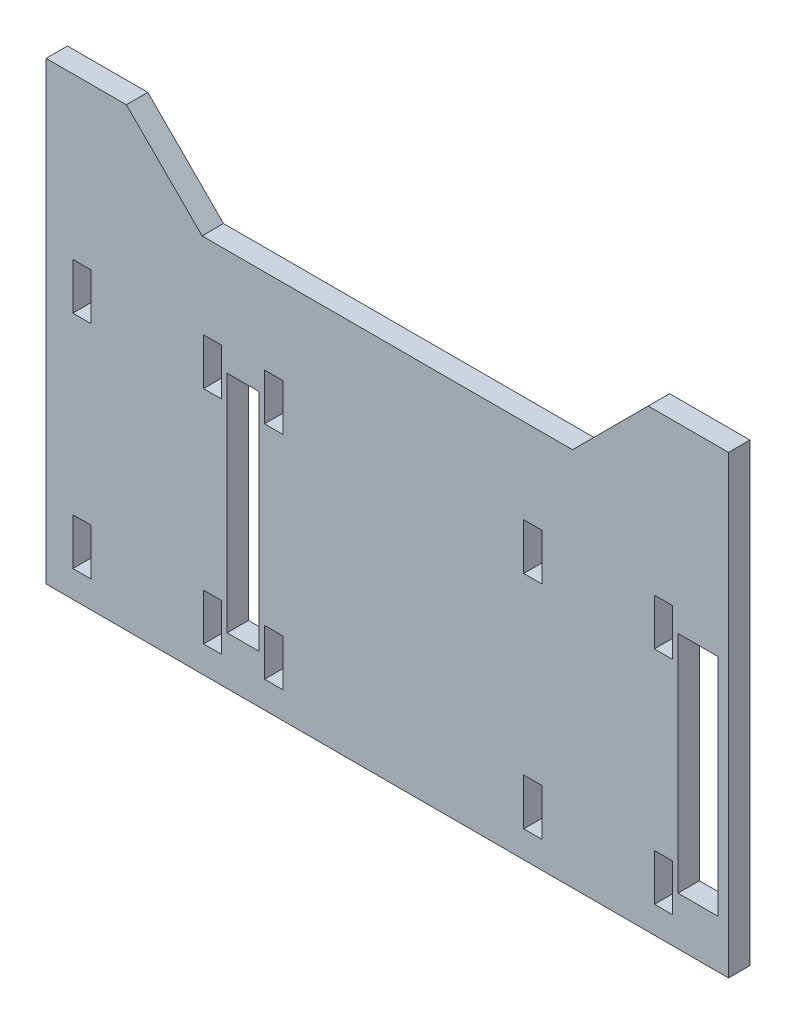
SolidWorks part; units mm, degrees
ref_plane "Front Plane" through (0, 0, 0) normal (0, 0, 1) x (1, 0, 0)
ref_plane "Top Plane" through (0, 0, 0) normal (0, 1, 0) x (1, 0, 0)
ref_plane "Right Plane" through (0, 0, 0) normal (1, 0, 0) x (0, 0, -1)
sketch "Sketch1" plane through (0, 0, 0) normal (0, 0, 1) x (1, 0, 0)
  line L0 (0, 66.0849) -> (0, -70.4198) construction
  line L6 (-37.3, 25) -> (-33.9, 25)
  line L7 (22.5, 25) -> (25.9, 25)
  line L8 (22.5, 25) -> (22.5, 16.3)
  line L9 (22.5, 16.3) -> (25.9, 16.3)
  line L10 (25.9, 25) -> (25.9, 16.3)
  line L11 (-103.5149, 0) -> (102.2922, 0) construction
  line L12 (22.5, -16.3) -> (25.9, -16.3)
  line L13 (22.5, -25) -> (22.5, -16.3)
  line L14 (25.9, -25) -> (25.9, -16.3)
  line L15 (22.5, -25) -> (25.9, -25)
  line L16 (-22.5, 25) -> (-25.9, 25)
  line L17 (-22.5, 25) -> (-22.5, 16.3)
  line L18 (-25.9, 25) -> (-25.9, 16.3)
  line L19 (-22.5, 16.3) -> (-25.9, 16.3)
  line L20 (-22.5, -16.3) -> (-25.9, -16.3)
  line L21 (-22.5, -25) -> (-22.5, -16.3)
  line L22 (-25.9, -25) -> (-25.9, -16.3)
  line L23 (-22.5, -25) -> (-25.9, -25)
  line L39 (46.9, 25) -> (50.3, 25)
  line L40 (46.9, 25) -> (46.9, 16.3)
  line L41 (46.9, 16.3) -> (50.3, 16.3)
  line L42 (50.3, 25) -> (50.3, 16.3)
  line L43 (46.9, -16.3) -> (50.3, -16.3)
  line L44 (46.9, -16.3) -> (46.9, -25)
  line L45 (46.9, -25) -> (50.3, -25)
  line L46 (50.3, -16.3) -> (50.3, -25)
  line L47 (-37.3, 25) -> (-37.3, 16.3)
  line L48 (-37.3, 16.3) -> (-33.9, 16.3)
  line L49 (-33.9, 25) -> (-33.9, 16.3)
  line L50 (-37.3, -16.3) -> (-33.9, -16.3)
  line L51 (-37.3, -16.3) -> (-37.3, -25)
  line L52 (-37.3, -25) -> (-33.9, -25)
  line L53 (-33.9, -16.3) -> (-33.9, -25)
  line L57 (-66.7, 30) -> (-66.7, -30)
  line L59 (-66.7, 30) -> (55.3, 30)
  line L60 (-61.7, 25) -> (-58.3, 25)
  line L61 (-61.7, 25) -> (-61.7, 16.3)
  line L62 (-61.7, 16.3) -> (-58.3, 16.3)
  line L63 (-58.3, 25) -> (-58.3, 16.3)
  line L64 (-61.7, -16.3) -> (-58.3, -16.3)
  line L65 (-61.7, -16.3) -> (-61.7, -25)
  line L66 (-61.7, -25) -> (-58.3, -25)
  line L67 (-58.3, -16.3) -> (-58.3, -25)
  line L68 (-66.7, -30) -> (55.3, -30)
  line L69 (55.3, 30) -> (60.7402, 30)
  line L70 (60.7402, 30) -> (60.7402, -30)
  line L71 (60.7402, -30) -> (55.3, -30)
  line L72 (51.3, 21) -> (58.8, 21)
  line L73 (58.8, 21) -> (58.8, -21)
  line L74 (58.8, -21) -> (51.3, -21)
  line L75 (51.3, -21) -> (51.3, 21)
  line L76 (-26.9, 21) -> (-32.9, 21)
  line L77 (-32.9, 21) -> (-32.9, -21)
  line L78 (-32.9, -21) -> (-26.9, -21)
  line L79 (-26.9, -21) -> (-26.9, 21)
  point P0 (0, 0)
  point P56 (50.3, 20.65)
  dimension "D2" = 60
  dimension "D3" = 8
  dimension "D4" = 1
  dimension "D5" = 3.4
  dimension "D6" = 8.7
  dimension "D7" = 45
  dimension "D8" = 21
  dimension "D9" = 21
  dimension "D10" = 5
  dimension "D11" = 5
  dimension "D12" = 7.5
  dimension "D13" = 9
  dimension "D14" = 9
  dimension "D15" = 1
  dimension "D16" = 1
  dimension "D17" = 9
  dimension "D18" = 9
extrude "Boss-Extrude1" add sketch "Sketch1" along normal blind 4
sketch "Sketch2" plane through (0, 0, 0) normal (0, 0, 1) x (1, 0, 0)
  line L0 (-66.7, 30) -> (-66.7, 55)
  line L1 (-66.7, 55) -> (-51.7, 55)
  line L2 (-51.7, 55) -> (-37.5579, 40.8579)
  line L7 (60.7402, 30) -> (-66.7, 30)
  line L8 (45.7402, 55) -> (60.7402, 55)
  line L9 (60.7402, 55) -> (60.7402, 30)
  line L10 (45.7402, 55) -> (31.5981, 40.8579)
  line L11 (31.5981, 40.8579) -> (-37.5579, 40.8579)
  line L12 (60.7402, -30) -> (60.7402, 30) construction
  dimension "D1" = 25
  dimension "D2" = 15
  dimension "D3" = 135
  dimension "D4" = 20
extrude "Boss-Extrude2" add sketch "Sketch2" along normal blind 4
